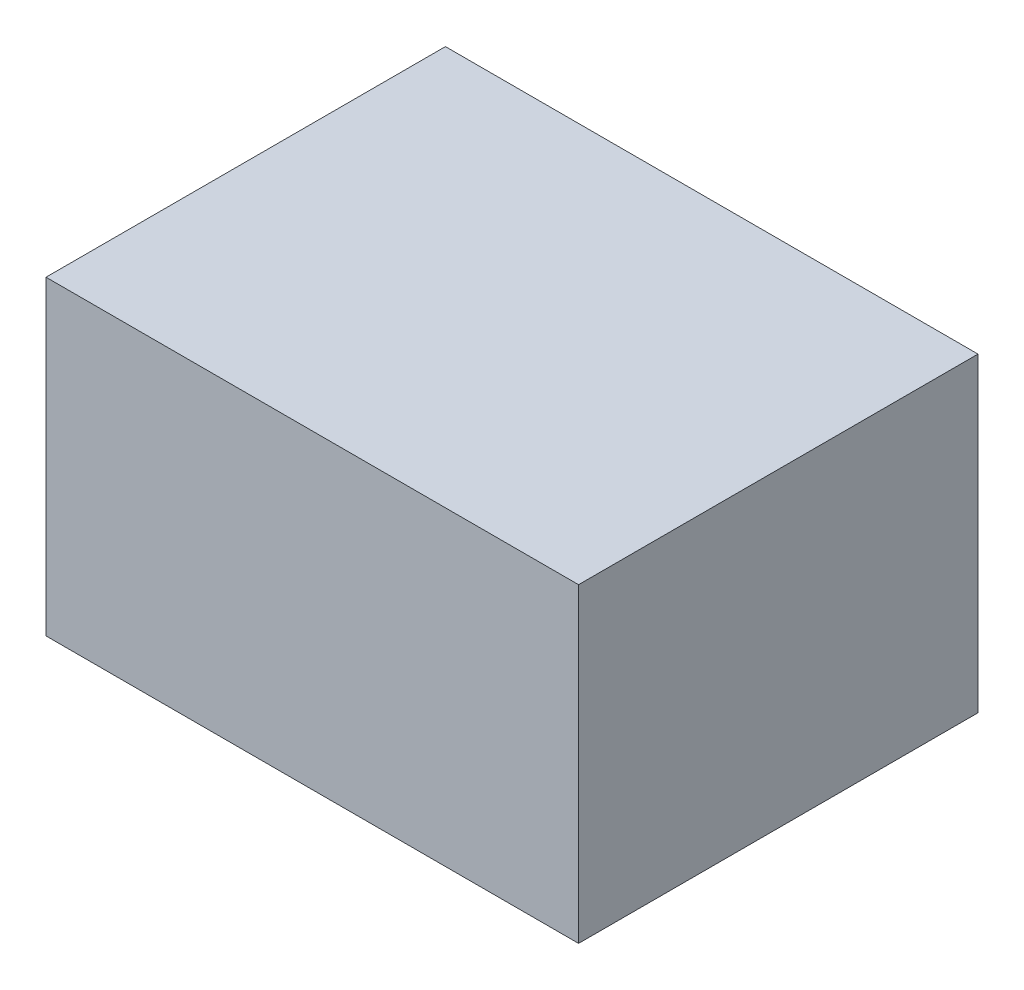
SolidWorks part; units mm, degrees
ref_plane "Front" through (0, 0, 0) normal (0, 0, 1) x (1, 0, 0)
ref_plane "Top" through (0, 0, 0) normal (0, 1, 0) x (1, 0, 0)
ref_plane "Right" through (0, 0, 0) normal (1, 0, 0) x (0, 0, -1)
ref_axis "Axis1" through (0, 0, 50) along (0, 0, -1)
sketch "Sketch1" plane through (0, 0, 0) normal (0, 1, 0) x (1, 0, 0)
  line L1 (-152.4, 114.3) -> (152.4, 114.3)
  line L2 (-152.4, 114.3) -> (-152.4, -114.3)
  line L3 (-152.4, -114.3) -> (152.4, -114.3)
  line L4 (152.4, 114.3) -> (152.4, -114.3)
  line L5 (-152.4, 114.3) -> (152.4, -114.3) construction
  line L6 (-152.4, -114.3) -> (152.4, 114.3) construction
  point P0 (0, 0)
  dimension "D1" = 304.8
  dimension "D2" = 228.6
extrude "Boss-Extrude1" add sketch "Sketch1" along normal blind 177.8
